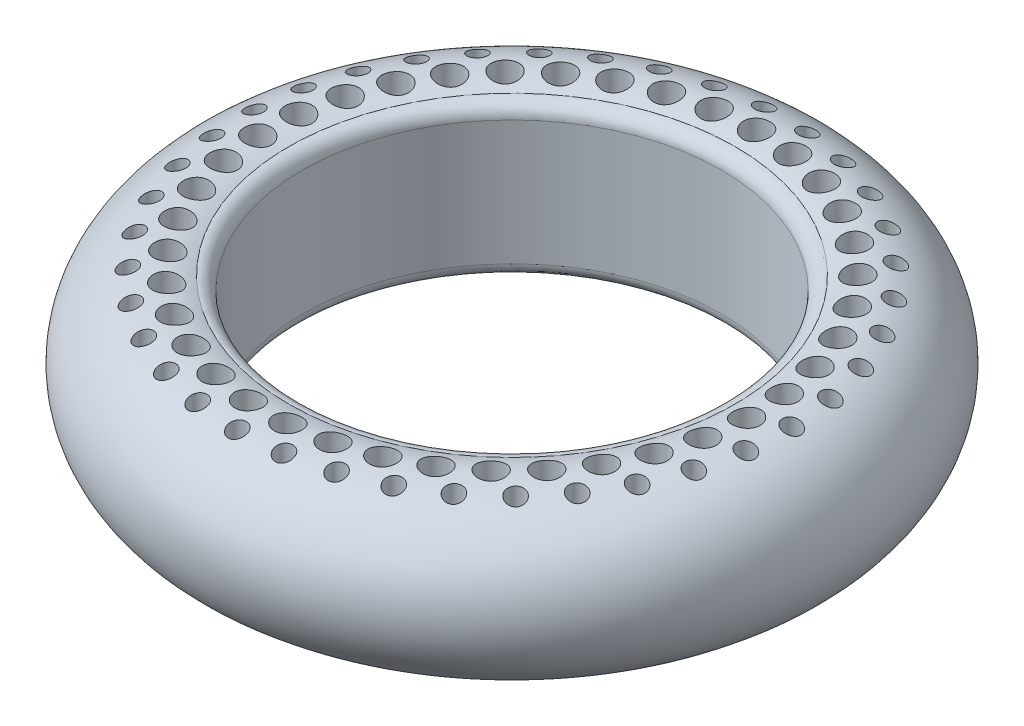
SolidWorks part; units mm, degrees
ref_plane "Front Plane" through (0, 0, 0) normal (0, 0, 1) x (1, 0, 0)
ref_plane "Top Plane" through (0, 0, 0) normal (0, 1, 0) x (1, 0, 0)
ref_plane "Right Plane" through (0, 0, 0) normal (1, 0, 0) x (0, 0, -1)
sketch "Sketch1" plane through (0, 0, 0) normal (0, 0, 1) x (1, 0, 0)
  line L0 (0, 0) -> (-46.25, 0) construction
  line L1 (0, 43.5581) -> (0, -37.5037) construction
  line L2 (-46.25, 13.75) -> (-46.25, -13.75)
  line L3 (-49.25, 16.75) -> (-49.25, -16.75) construction
  line L4 (-72.75, 16.75) -> (-72.75, -16.75) construction
  line L5 (-72.75, 16.75) -> (-36.9549, 16.75) construction
  line L6 (-72.75, -16.75) -> (-36.9549, -16.75) construction
  arc A0 (-46.25, 13.75) -> (-49.25, 16.75) centre (-49.25, 13.75) ccw
  arc A1 (-49.25, 16.75) -> (-49.25, -16.75) centre (-55.0306, 0) ccw
  arc A2 (-46.25, -13.75) -> (-49.25, -16.75) centre (-49.25, -13.75) cw
  dimension "D1" = 92.5
  dimension "D2" = 27.5
  dimension "D3" = 26.5
  dimension "D4" = 33.5
revolve "Revolve1" add sketch "Sketch1" angle 360 about L1
sketch "Sketch2" plane through (0, 0, 0) normal (0, 1, 0) x (1, 0, 0)
  line L0 (0, 0) -> (0, 54) construction
  line L1 (0, 0) -> (-4.1854, 59.8538) construction
  circle A0 centre (0, 54) radius 3
  circle A1 centre (-4.1854, 59.8538) radius 2
  dimension "D1" = 4
  dimension "D2" = 6
  dimension "D3" = 4
  dimension "D4" = 54
  dimension "D5" = 60
extrude "Cut-Extrude1" cut sketch "Sketch2" against normal through all and the other way through all
pattern_circular "CirPattern1" count 39 over 360 about axis through (0, 43.5581, 0) along (0, 1, 0) of "Cut-Extrude1"
